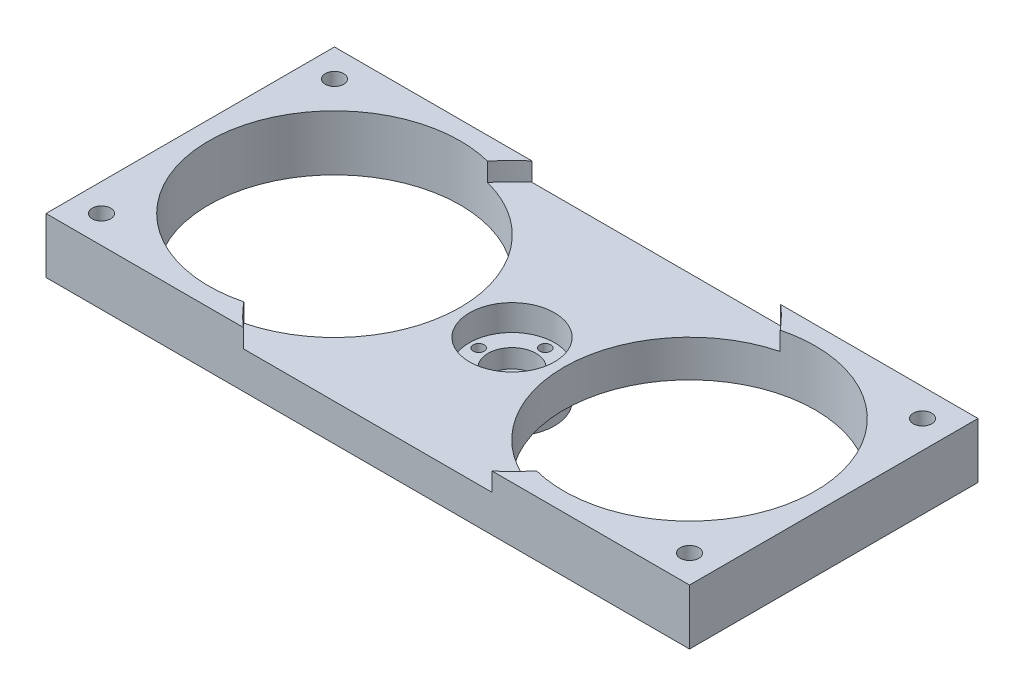
SolidWorks part; units mm, degrees
ref_plane "Front Plane" through (0, 0, 0) normal (0, 0, 1) x (1, 0, 0)
ref_plane "Top Plane" through (0, 0, 0) normal (0, 1, 0) x (1, 0, 0)
ref_plane "Right Plane" through (0, 0, 0) normal (1, 0, 0) x (0, 0, -1)
sketch "Sketch1" plane through (0, 0, 0) normal (0, 1, 0) x (1, 0, 0)
  line L0 (0, 0) -> (9, 0) construction
  line L1 (0, 0) -> (-9, 0) construction
  line L2 (0, 0) -> (0, -9) construction
  line L3 (0, 0) -> (0, 9) construction
  line L4 (0, 0) -> (48, 0) construction
  line L5 (0, 0) -> (-48, 0) construction
  line L6 (48, 0) -> (82, 0) construction
  line L7 (82, 0) -> (87, 0) construction
  line L8 (48, 0) -> (48, 34) construction
  line L9 (48, 34) -> (48, 39) construction
  line L10 (-48, 0) -> (-82, 0) construction
  line L11 (-82, 0) -> (-87, 0) construction
  line L12 (-48, 0) -> (-48, -34) construction
  line L13 (-48, -34) -> (-48, -39) construction
  line L14 (-87, -27.7881) -> (-79.5, -27.7881) construction
  line L15 (87, 39) -> (-87, 39)
  line L16 (87, 39) -> (87, -39)
  line L17 (87, -39) -> (-87, -39)
  line L18 (-87, 39) -> (-87, -39)
  line L19 (-79.5, 39) -> (-79.5, 31.5) construction
  line L20 (87, 31.5) -> (79.5, 31.5) construction
  line L21 (79.5, 31.5) -> (79.5, -31.5) construction
  circle A0 centre (0, 0) radius 2.5
  circle A1 centre (0, 0) radius 6.5
  circle A2 centre (0, 9) radius 1.5
  circle A3 centre (9, 0) radius 1.5
  circle A4 centre (0, -9) radius 1.5
  circle A5 centre (-9, 0) radius 1.5
  circle A6 centre (0, 0) radius 11.5
  circle A7 centre (48, 0) radius 34
  circle A8 centre (-48, 0) radius 34
  arc A9 (-39.5859, -32.9424) -> (-33.6341, -39) centre (0, 0) ccw
  arc A10 (-33.6341, 39) -> (-39.5859, 32.9424) centre (0, 0) ccw
  arc A11 (39.5859, 32.9424) -> (33.6341, 39) centre (0, 0) ccw
  arc A12 (33.6341, -39) -> (39.5859, -32.9424) centre (0, 0) ccw
  circle A13 centre (-79.5, -31.5) radius 2.5
  circle A14 centre (-79.5, 31.5) radius 2.5
  circle A15 centre (79.5, 31.5) radius 2.5
  circle A16 centre (79.5, -31.5) radius 2.5
extrude "Boss-Extrude1" add sketch "Sketch1" along normal blind 3 contours A1 A0 region at (-6.3162, 0, 0)
extrude "Boss-Extrude2" add sketch "Sketch1<3>" along normal blind 8 separate body contours A3 | A1 | A6 | A4 | A5 | A2 region at (9, 0, 0)
sketch "Sketch1<3>" plane through (0, 0, 0) normal (0, 1, 0) x (1, 0, 0) same geometry as "Sketch1"
extrude "Boss-Extrude3" add sketch "Sketch1<4>" along normal blind 15 contours L17 A12 A7 A11 L15 A10 A8 A9 A6 region at (35.9423, 0, -35.3152)
sketch "Sketch1<4>" plane through (0, 0, 0) normal (0, 1, 0) x (1, 0, 0) same geometry as "Sketch1"
extrude "Boss-Extrude4" add sketch "Sketch1<5>" along normal blind 20 contours A10 L15 L18 L17 A9 A8 A14 A13 | A12 L17 L16 L15 A11 A7 A16 A15 region at (86.0549, 0, 0) region at (-37.4092, 0, -36.7565)
sketch "Sketch1<5>" plane through (0, 0, 0) normal (0, 1, 0) x (1, 0, 0) same geometry as "Sketch1"
sketch "Sketch3" plane through (0, 0, 0) normal (0, -1, 0) x (1, 0, 0)
  line L4 (87, 39) -> (-87, 39)
  line L5 (-87, 39) -> (-87, -39)
  line L6 (-87, -39) -> (87, -39)
  line L7 (87, -39) -> (87, 39)
  line L8 (87, 39) -> (-87, 39)
  line L9 (-87, 39) -> (-87, -39)
  line L10 (-87, -39) -> (87, -39)
  line L11 (87, -39) -> (87, 39)
  circle A0 centre (0, 0) radius 11.5 construction
  circle A1 centre (0, 0) radius 11.5
  dimension "D1" = 0
extrude "Cut-Extrude1" cut sketch "Sketch3" against normal blind 5
